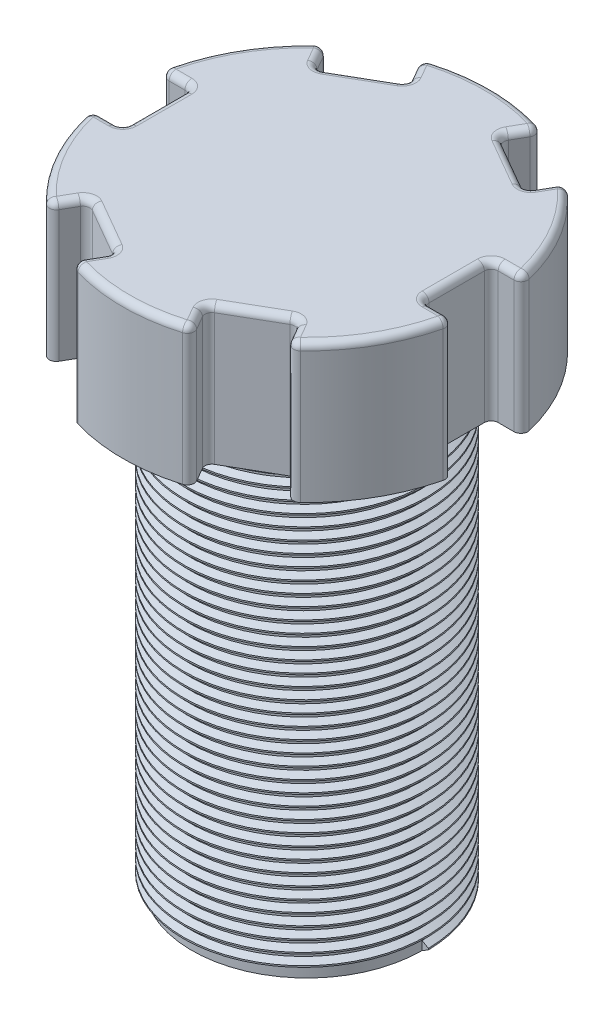
SolidWorks part; units mm, degrees
ref_plane "Front" through (0, 0, 0) normal (0, 0, 1) x (1, 0, 0)
ref_plane "Top" through (0, 0, 0) normal (0, 1, 0) x (1, 0, 0)
ref_plane "Right" through (0, 0, 0) normal (1, 0, 0) x (0, 0, -1)
sketch "Sketch1" plane through (0, 0, 0) normal (0, 1, 0) x (1, 0, 0)
  circle A0 centre (0, 0) radius 4
  dimension "D1" = 8
extrude "Boss-Extrude1" add sketch "Sketch1" along normal blind 3
sketch "Sketch2" plane through (0, 0, 0) normal (0, -1, 0) x (1, 0, 0)
  circle A0 centre (0, 0) radius 2.5
extrude "Boss-Extrude2" add sketch "Sketch2" along normal blind 10
thread "Thread1" pitch 0.25 profile "Thread Profile1" start angle 0, offset 0, length 0, pitch 0.25, diameter 5
ref_plane "Plane1" through (2.5, -10, 0) normal (0, 0, 1) x (1, 0, 0)
sketch "Thread Profile1" plane through (2.5, -10, 0) normal (0, 0, 1) x (1, 0, 0)
  line L0 (0, 0) -> (0, 0.25) construction
  line L1 (0, 0) -> (0.1353, 0.0781)
  line L2 (0.1353, 0.0781) -> (0.1353, 0.1094)
  line L3 (0.1353, 0.1094) -> (0, 0.1875)
  line L4 (0.1353, 0.0937) -> (0, 0.0937) construction
  line L11 (0, 0) -> (0, 0.1875)
  point P2 (0, 0)
  dimension "Pitch" = 0.25
  dimension "Profile_Angle" = 60
  dimension "Profile_Land" = 0.0312
  dimension "Profile_Height" = 0.1353
sketch "Sketch8" plane through (0, 3, 0) normal (0, 1, 0) x (1, 0, 0)
  line L1 (3.25, -0.75) -> (4.75, -0.75)
  line L2 (3.25, -0.75) -> (3.25, 0.75)
  line L3 (3.25, 0.75) -> (4.75, 0.75)
  line L4 (4.75, -0.75) -> (4.75, 0.75)
  line L5 (3.25, -0.75) -> (4.75, 0.75) construction
  line L6 (3.25, 0.75) -> (4.75, -0.75) construction
  circle A0 centre (0, 0) radius 4 construction
  point P0 (4, 0)
  dimension "D1" = 1.5
  dimension "D2" = 1.5
extrude "Cut-Extrude1" cut sketch "Sketch8" against normal blind 3
fillet "Fillet1" radius 0.15 1 edges at (3.9291, 1.5, -0.75)
fillet "Fillet2" radius 0.15 1 edges at (3.25, 1.5, 0.75)
fillet "Fillet3" radius 0.15 1 edges at (3.9291, 1.5, 0.75)
fillet "Fillet4" radius 0.15 1 edges at (3.25, 1.5, -0.75)
pattern_circular "CirPattern1" count 6 over 360 about axis through (0, 0, 0) along (0, 1, 0) of "Cut-Extrude1", "Fillet1", "Fillet3", "Fillet2", "Fillet4"
fillet "Fillet5" radius 0.15 48 edges at (-2.6296, 3, -2.9403) (-2.4354, 3, -2.7182) (-2.2584, 3, -2.4996) (-1.625, 3, -2.8146) (-1.0355, 3, -3.2057) (-1.1363, 3, -3.4682) (-1.2316, 3, -3.7474) (0, 3, -4) (1.2316, 3, -3.7474) (1.1363, 3, -3.4682) (1.0355, 3, -3.2057) (1.625, 3, -2.8146) (2.2584, 3, -2.4996) (2.4354, 3, -2.7182) (2.6296, 3, -2.9403) (3.4641, 3, -2) (3.8611, 3, -0.8072) (3.5717, 3, -0.75) (3.2939, 3, -0.7061) (3.25, 3, 0) (3.2939, 3, 0.7061) (3.5717, 3, 0.75) (3.8611, 3, 0.8072) (3.4641, 3, 2) (2.6296, 3, 2.9403) (2.4354, 3, 2.7182) (2.2584, 3, 2.4996) (1.625, 3, 2.8146) (1.0355, 3, 3.2057) (1.1363, 3, 3.4682) (1.2316, 3, 3.7474) (0, 3, 4) (-1.2316, 3, 3.7474) (-1.1363, 3, 3.4682) (-1.0355, 3, 3.2057) (-1.625, 3, 2.8146) (-2.2584, 3, 2.4996) (-2.4354, 3, 2.7182) (-2.6296, 3, 2.9403) (-3.4641, 3, 2) (-3.8611, 3, 0.8072) (-3.5717, 3, 0.75) (-3.2939, 3, 0.7061) (-3.25, 3, 0) (-3.2939, 3, -0.7061) (-3.5717, 3, -0.75) (-3.8611, 3, -0.8072) (-3.4641, 3, -2)
